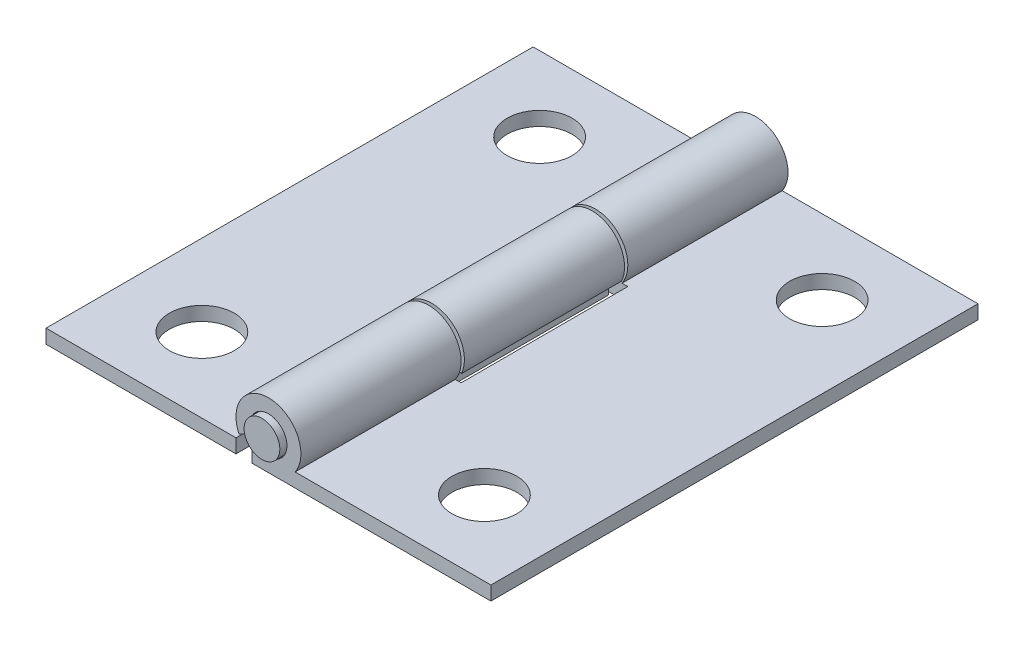
SolidWorks part; units mm, degrees
note: The reader was unsure of these and kept them because the rebuilt part matched: shared geometry of "Sketch2<4>", "Sketch2<5>".
ref_plane "Front Plane" through (0, 0, 0) normal (0, 0, 1) x (1, 0, 0)
ref_plane "Top Plane" through (0, 0, 0) normal (0, 1, 0) x (1, 0, 0)
ref_plane "Right Plane" through (0, 0, 0) normal (1, 0, 0) x (0, 0, -1)
sketch "Sketch1" plane through (0, 0, 0) normal (0, 1, 0) x (1, 0, 0)
  line L0 (14.859, 2.1749) -> (19.939, 2.1749) construction
  line L1 (0, 0) -> (14.859, 0)
  line L2 (0, 0) -> (0, 38.1)
  line L3 (0, 38.1) -> (14.859, 38.1)
  line L4 (14.859, 0) -> (14.859, 38.1)
  line L5 (19.939, 38.1) -> (34.798, 38.1)
  line L6 (19.939, 38.1) -> (19.939, 0)
  line L7 (19.939, 0) -> (34.798, 0)
  line L8 (34.798, 38.1) -> (34.798, 0)
  line L9 (28.448, 32.258) -> (28.448, 5.842) construction
  line L10 (34.798, 19.05) -> (28.448, 19.05) construction
  line L11 (17.399, 2.1749) -> (17.399, 27.3298) construction
  line L12 (14.859, 25.3153) -> (18.669, 25.3153)
  line L13 (18.669, 25.3153) -> (18.669, 12.7847)
  line L14 (18.669, 12.7847) -> (14.859, 12.7847)
  line L15 (19.939, 0) -> (16.129, 0)
  line L16 (16.129, 0) -> (16.129, 12.5307)
  line L17 (16.129, 12.5307) -> (19.939, 12.5307)
  line L18 (16.129, 0) -> (19.939, 0)
  line L19 (17.399, 35.9251) -> (17.399, 10.7702) construction
  line L20 (14.859, 35.9251) -> (19.939, 35.9251) construction
  line L21 (16.129, 38.1) -> (19.939, 38.1)
  line L22 (16.129, 25.5693) -> (19.939, 25.5693)
  line L23 (16.129, 38.1) -> (16.129, 25.5693)
  line L24 (19.939, 38.1) -> (16.129, 38.1)
  circle A0 centre (28.448, 32.258) radius 2.54
  circle A1 centre (28.448, 5.842) radius 2.54
  circle A2 centre (6.35, 5.842) radius 2.54
  circle A3 centre (6.35, 32.258) radius 2.54
  point P37 (14.986, 11.8916)
  dimension "D6" = 5.08
  dimension "D1" = 5.08
  dimension "D2" = 34.798
  dimension "D3" = 38.1
  dimension "D4" = 6.35
  dimension "D5" = 26.416
  dimension "D7" = 1.27
  dimension "D8" = 1.27
  dimension "D9" = 0.254
extrude "Boss-Extrude1" add sketch "Sketch1" along normal blind 1.0922 contours L1 L4 L3 L2 A2 A3 | L8 L5 L6 L7 A1 A0 | L14 L13 L12 L4 | L21 L23 L22 L6 | L17 L16 L15 L6
sketch "Sketch2" plane through (0, 0, 0) normal (0, 0, 1) x (1, 0, 0)
  line L0 (0, 1.0922) -> (34.798, 1.0922) construction
  line L1 (17.399, 1.0922) -> (17.399, 2.54) construction
  line L2 (16.129, 0) -> (34.798, 0) construction
  line L3 (17.399, 1.0922) -> (19.486, 1.0922)
  line L4 (17.399, 1.0922) -> (15.312, 1.0922)
  line L5 (18.7112, 1.9281) -> (19.701, 1.4665)
  line L6 (16.0868, 1.9281) -> (15.097, 1.4665)
  circle A0 centre (17.399, 2.54) radius 2.54
  circle A1 centre (17.399, 2.54) radius 1.4478
  line M5 (34.798, 1.0922) -> (16.129, 1.0922)
  dimension "D1" = 5.08
  dimension "D2" = 25
extrude "Boss-Extrude3" add sketch "Sketch2" against normal up to surface (12.5307 mm away) contours A1 A0 L5 M5 | A1 L5 A0 L6 up to face at (18.034, 0.5461, -12.5307)
ref_plane "Plane1" through (0, 0, -19.05) normal (0, 0, -1) x (-1, 0, 0)
extrude "Boss-Extrude4" add sketch "Sketch2<4>" against normal up to surface (12.5307 mm away) from surface at -25.5693 contours A1 A0 L5 M5 | A1 L5 A0 L6 up to face at (7.4295, 0.5461, -38.1) starting at face at (18.034, 0.5461, -25.5693)
sketch "Sketch2<4>" plane through (0, 0, 0) normal (0, 0, 1) x (1, 0, 0) same geometry as "Sketch2"
extrude "Boss-Extrude5" add sketch "Sketch2<5>" against normal up to surface (12.5307 mm away) from surface at -12.7847 contours A1 L6 A0 L4 M5 | A1 L5 A0 L6 up to face at (16.764, 0.5461, -25.3153) starting at face at (16.764, 0.5461, -12.7847)
sketch "Sketch2<5>" plane through (0, 0, 0) normal (0, 0, 1) x (1, 0, 0) same geometry as "Sketch2"
sketch "Sketch3" plane through (0, 0, -38.1) normal (0, 0, -1) x (-1, 0, 0)
  arc A0 (-16.0868, 1.9281) -> (-17.399, 1.0922) centre (-17.399, 2.54) ccw construction
  arc A1 (-16.0868, 1.9281) -> (-17.399, 1.0922) centre (-17.399, 2.54) ccw construction
  circle A2 centre (-17.399, 2.54) radius 1.397
  dimension "D1" = 0.0508
extrude "Boss-Extrude6" add sketch "Sketch3" against normal offset from surface (39.116 mm away) 0.508 from offset 0.508 separate body up to face at (21.46, 1.7257, 0) offset beyond the face yes
other "Save Bodies1"
